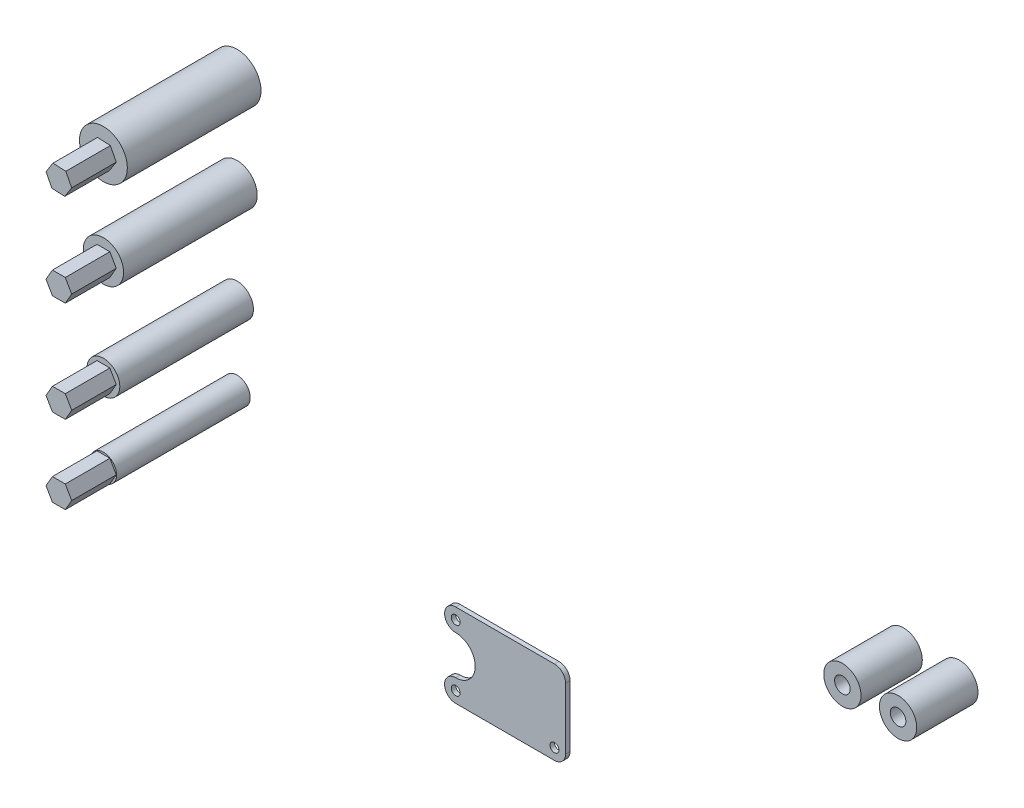
SolidWorks part; units mm, degrees
ref_plane "Front Plane" through (0, 0, 0) normal (0, 0, 1) x (1, 0, 0)
ref_plane "Top Plane" through (0, 0, 0) normal (0, 1, 0) x (1, 0, 0)
ref_plane "Right Plane" through (0, 0, 0) normal (1, 0, 0) x (0, 0, -1)
sketch "Sketch1" plane through (0, 0, 0) normal (0, 0, 1) x (1, 0, 0)
  line L0 (42.5252, 85.2495) -> (55.5016, 85.2495) construction
  line L1 (58.7537, 81.2495) -> (58.7537, 83.2495)
  line L2 (39.0352, 83.2495) -> (39.0252, 83.2495)
  line L3 (39.0252, 79.2495) -> (56.7537, 79.2495)
  line L5 (-0.0481, 105.8254) -> (0.9333, 107.5254)
  line L6 (0.9333, 107.5254) -> (-0.0481, 109.2254)
  line L7 (-0.0481, 109.2254) -> (-2.0111, 109.2254)
  line L8 (-2.0111, 109.2254) -> (-2.9926, 107.5254)
  line L9 (-2.9926, 107.5254) -> (-2.0111, 105.8254)
  line L10 (-2.0111, 105.8254) -> (-0.0481, 105.8254)
  line L11 (0.2405, 119.3642) -> (1.5107, 121.5642)
  line L12 (1.5107, 121.5642) -> (0.2405, 123.7642)
  line L13 (0.2405, 123.7642) -> (-2.2998, 123.7642)
  line L14 (-2.2998, 123.7642) -> (-3.57, 121.5642)
  line L15 (-3.57, 121.5642) -> (-2.2998, 119.3642)
  line L16 (-2.2998, 119.3642) -> (0.2405, 119.3642)
  line L17 (0.5292, 136.9341) -> (2.088, 139.6341)
  line L18 (2.088, 139.6341) -> (0.5292, 142.3341)
  line L19 (0.5292, 142.3341) -> (-2.5885, 142.3341)
  line L20 (-2.5885, 142.3341) -> (-4.1473, 139.6341)
  line L21 (-4.1473, 139.6341) -> (-2.5885, 136.9341)
  line L22 (-2.5885, 136.9341) -> (0.5292, 136.9341)
  line L23 (2.088, 139.6341) -> (2.588, 139.6341) construction
  line L24 (1.5107, 121.5642) -> (1.9107, 121.5642) construction
  line L25 (0.9333, 107.5254) -> (1.3333, 107.5254) construction
  line L26 (42.5252, 86.7395) -> (42.5252, 86.7595)
  line L27 (39.0352, 90.2495) -> (39.0252, 90.2495)
  line L28 (39.0252, 94.2495) -> (51.5016, 94.2495)
  line L29 (53.5016, 87.2495) -> (53.5016, 92.2495)
  line L30 (55.5016, 85.2495) -> (56.7537, 85.2495)
  line L31 (58.7537, 83.2495) -> (58.7537, 92.2495)
  line L32 (56.7537, 94.2495) -> (51.5016, 94.2495)
  line L33 (2.6654, 156.2509) -> (3.2654, 156.2509) construction
  line L34 (2.6654, 156.2509) -> (0.8179, 159.4509)
  line L35 (0.8179, 159.4509) -> (-2.8772, 159.4509)
  line L36 (-2.8772, 159.4509) -> (-4.7247, 156.2509)
  line L37 (-4.7247, 156.2509) -> (-2.8772, 153.0509)
  line L38 (-2.8772, 153.0509) -> (0.8179, 153.0509)
  line L39 (0.8179, 153.0509) -> (2.6654, 156.2509)
  circle A0 centre (39.0252, 81.2495) radius 2
  circle A1 centre (56.7537, 81.2495) radius 2
  circle A2 centre (39.0252, 81.2495) radius 0.8
  circle A3 centre (56.7537, 81.2495) radius 0.8
  arc A4 (58.7537, 92.2495) -> (56.7537, 94.2495) centre (56.7537, 92.2495) ccw
  arc A5 (39.0352, 83.2495) -> (42.5252, 86.7395) centre (39.0352, 86.7395) ccw
  circle A6 centre (-1.0296, 107.5254) radius 1.7 construction
  circle A7 centre (-1.0296, 121.5642) radius 2.2 construction
  circle A8 centre (-1.0296, 139.6341) radius 2.7 construction
  circle A9 centre (-1.0296, 107.5254) radius 2.363
  circle A10 centre (-1.0296, 121.5642) radius 2.9403
  circle A11 centre (-1.0296, 139.6341) radius 3.6177
  circle A12 centre (-1.0296, 139.6341) radius 1.5
  circle A13 centre (-1.0296, 121.5642) radius 1.25
  circle A14 centre (-1.0296, 107.5254) radius 1.05
  circle A15 centre (39.0252, 92.2495) radius 2
  circle A16 centre (39.0252, 92.2495) radius 0.8
  arc A17 (42.5252, 86.7595) -> (39.0352, 90.2495) centre (39.0352, 86.7595) ccw
  circle A18 centre (-1.0296, 156.2509) radius 3.2 construction
  circle A19 centre (-1.0296, 156.2509) radius 4.295
  circle A20 centre (-1.0296, 156.2509) radius 1.75
  circle B0 centre (78.6519, 127.0575) radius 1.4
  circle B1 centre (78.6519, 127.0575) radius 3.35
  circle B2 centre (78.736, 101.9939) radius 0.85
  circle B3 centre (78.736, 101.9939) radius 2.9
  circle B4 centre (78.736, 114.8621) radius 1.1
  circle B5 centre (78.736, 114.8621) radius 2.7
  circle B6 centre (88.6519, 127.0575) radius 1.4
  circle B7 centre (88.6519, 127.0575) radius 3.35
  circle B8 centre (98.6519, 127.0575) radius 1.4
  circle B9 centre (98.6519, 127.0575) radius 3.35
  circle B10 centre (108.6519, 127.0575) radius 1.4
  circle B11 centre (108.6519, 127.0575) radius 3.35
  circle B12 centre (118.6519, 127.0575) radius 1.4
  circle B13 centre (118.6519, 127.0575) radius 3.35
  circle B14 centre (128.6519, 127.0575) radius 1.4
  circle B15 centre (128.6519, 127.0575) radius 3.35
  circle B16 centre (88.736, 101.9939) radius 0.85
  circle B17 centre (88.736, 101.9939) radius 2.9
  circle B18 centre (98.736, 101.9939) radius 0.85
  circle B19 centre (98.736, 101.9939) radius 2.9
  circle B20 centre (108.736, 101.9939) radius 0.85
  circle B21 centre (108.736, 101.9939) radius 2.9
  circle B22 centre (88.736, 114.8621) radius 1.1
  circle B23 centre (88.736, 114.8621) radius 2.7
  circle B24 centre (76.8787, 139.9756) radius 1.6
  circle B25 centre (76.8787, 139.9756) radius 4
  circle B26 centre (86.8787, 139.9756) radius 1.6
  circle B27 centre (86.8787, 139.9756) radius 4
  dimension "D1" = 4
  dimension "D2" = 1.6
  dimension "D4" = 2
  dimension "D6" = 7
  dimension "D11" = 3
  dimension "D12" = 2.5
  dimension "D13" = 2.1
  dimension "D18" = 4
  dimension "D19" = 1.6
  dimension "D20" = 3.5
  dimension "D21" = 6.4
  dimension "D22" = 0.6
  dimension "D26" = 2
  dimension "D27" = 3.5
  dimension "D5" = 3.49
  dimension "D28" = 3.49
  dimension "D3" = 4
  dimension "D7" = 17.7284
  dimension "D8" = 3.4
  dimension "D9" = 5.4
  dimension "D10" = 4.4
  dimension "D14" = 0.5
  dimension "D15" = 0.4
  dimension "D16" = 0.4
  dimension "D17" = 11
  dimension "D23" = 6
  dimension "D24" = 4
  dimension "D25" = 2
sketch_block_instance "M2.5 spacer-10"
sketch_block "M2.5 spacer" parameters "D1"=2.8, "D3"=6.7, "D4"=2.7, "D2"=4.7
sketch_block_instance "M1.6 spacer-11"
sketch_block "M1.6 spacer" parameters "D1"=1.7, "D3"=5.8, "D4"=1.8, "D2"=3.8
sketch_block_instance "M2 spacer-4"
sketch_block "M2 spacer" parameters "D1"=2.2, "D3"=1, "D4"=2.2, "D2"=3.8
sketch_block_instance "M2.5 spacer-15"
sketch_block_instance "M2.5 spacer-16"
sketch_block_instance "M2.5 spacer-17"
sketch_block_instance "M2.5 spacer-18"
sketch_block_instance "M2.5 spacer-19"
sketch_block_instance "M1.6 spacer-14"
sketch_block_instance "M1.6 spacer-15"
sketch_block_instance "M1.6 spacer-16"
sketch_block_instance "M2 spacer-6"
sketch_block_instance "M3 spacer-1"
sketch_block "M3 spacer" parameters "D1"=3.2, "D2"=8, "D3"=5.6
sketch_block_instance "M3 spacer-2"
extrude "Boss-Extrude1" add sketch "Sketch1" along normal blind 8 contours A11 L22 L21 L20 L19 L18 L17 | A10 L16 L15 L14 L13 L12 L11 | A9 L10 L9 L8 L7 L6 L5 | A19 L39 L38 L37 L36 L35 L34 region at (-3.3258, 107.5254, 0) region at (-3.8868, 121.5642, 0) region at (-4.545, 139.6341, 0) region at (-5.2032, 156.2509, 0)
extrude "Boss-Extrude2" add sketch "Sketch1<3>" along normal blind 16 from surface contours L9 L10 L5 L6 L7 L8 A14 | A9 L10 L9 L8 L7 L6 L5 | A10 L16 L15 L14 L13 L12 L11 | L15 L16 L11 L12 L13 L14 A13 | A11 L22 L21 L20 L19 L18 L17 | L21 L22 L17 L18 L19 L20 A12 | A19 L39 L38 L37 L36 L35 L34 | L38 L39 L34 L35 L36 L37 A20 region at (-1.0296, 105.8773, 0) region at (-1.0296, 119.4314, 0) region at (-1.0296, 137.0166, 0) region at (1.657, 154.6998, 0) region at (-3.3258, 107.5254, 0) region at (-3.8868, 121.5642, 0) region at (-4.545, 139.6341, 0) region at (-5.2032, 156.2509, 0) starting at face at (-1.0296, 139.6341, 8)
sketch "Sketch1<3>" plane through (0, 0, 0) normal (0, 0, 1) x (1, 0, 0) same geometry as "Sketch1"
sketch "Sketch2" plane through (0, 0, 24) normal (0, 0, 1) x (1, 0, 0)
  circle A0 centre (-1.0296, 156.2509) radius 4.295 construction
  line B0 (0.1251, 137.6341) -> (1.2798, 139.6341)
  line B1 (1.2798, 139.6341) -> (0.1251, 141.6341)
  line B2 (0.1251, 141.6341) -> (-2.1843, 141.6341)
  line B3 (-2.1843, 141.6341) -> (-3.339, 139.6341)
  line B4 (-3.339, 139.6341) -> (-2.1843, 137.6341)
  line B5 (-2.1843, 137.6341) -> (0.1251, 137.6341)
  circle B6 centre (-1.0296, 139.6341) radius 2 construction
  line B7 (0.1251, 119.5642) -> (1.2798, 121.5642)
  line B8 (1.2798, 121.5642) -> (0.1251, 123.5642)
  line B9 (0.1251, 123.5642) -> (-2.1843, 123.5642)
  line B10 (-2.1843, 123.5642) -> (-3.339, 121.5642)
  line B11 (-3.339, 121.5642) -> (-2.1843, 119.5642)
  line B12 (-2.1843, 119.5642) -> (0.1251, 119.5642)
  circle B13 centre (-1.0296, 121.5642) radius 2 construction
  line B14 (0.1251, 105.5254) -> (1.2798, 107.5254)
  line B15 (1.2798, 107.5254) -> (0.1251, 109.5254)
  line B16 (0.1251, 109.5254) -> (-2.1843, 109.5254)
  line B17 (-2.1843, 109.5254) -> (-3.339, 107.5254)
  line B18 (-3.339, 107.5254) -> (-2.1843, 105.5254)
  line B19 (-2.1843, 105.5254) -> (0.1251, 105.5254)
  circle B20 centre (-1.0296, 107.5254) radius 2 construction
  line B21 (0.0317, 154.1998) -> (1.2773, 156.1444)
  line B22 (1.2773, 156.1444) -> (0.216, 158.1955)
  line B23 (0.216, 158.1955) -> (-2.0909, 158.302)
  line B24 (-2.0909, 158.302) -> (-3.3366, 156.3573)
  line B25 (-3.3366, 156.3573) -> (-2.2753, 154.3062)
  line B26 (-2.2753, 154.3062) -> (0.0317, 154.1998)
  circle B27 centre (-1.0296, 156.2509) radius 2 construction
sketch_block_instance "T4-hex-1"
sketch_block "T4-hex" parameters "D1"=4
sketch_block_instance "T4-hex-2"
sketch_block_instance "T4-hex-3"
sketch_block_instance "T4-hex-4"
extrude "Boss-Extrude3" add sketch "Sketch2" along normal blind 8
chamfer "Chamfer1" distance 1 angle 60 1 edges at (0.0204, 107.5254, 24) first distance on face at (0.0204, 107.5254, 24)
chamfer "Chamfer2" distance 1.2 angle 60 1 edges at (0.2204, 121.5642, 24) first distance on face at (0.2204, 121.5642, 24)
chamfer "Chamfer3" distance 1.4 angle 60 1 edges at (0.4704, 139.6341, 24) first distance on face at (0.4704, 139.6341, 24)
chamfer "Chamfer4" distance 1.6 angle 60 1 edges at (0.7204, 156.2509, 24) first distance on face at (0.7204, 156.2509, 24)
extrude "Boss-Extrude4" add sketch "Sketch1<5>" along normal blind 0.8 separate body contours L30 L29 L28 A15 L27 A17 L26 A5 L2 A0 L3 A1 L1 | A0 A2 | A1 A3 | A15 A16 region at (49.5289, 87.0262, 0) region at (58.1279, 79.8753, 0) region at (37.0818, 81.2495, 0) region at (40.3994, 93.6237, 0)
sketch "Sketch1<5>" plane through (0, 0, 0) normal (0, 0, 1) x (1, 0, 0) same geometry as "Sketch1"
extrude "Boss-Extrude5" add sketch "Sketch1<7>" along normal blind 11 separate body contours B15 B14 | B13 B12 region at (115.3966, 127.0575, 0) region at (125.3966, 127.0575, 0)
sketch "Sketch1<7>" plane through (0, 0, 0) normal (0, 0, 1) x (1, 0, 0) same geometry as "Sketch1"
